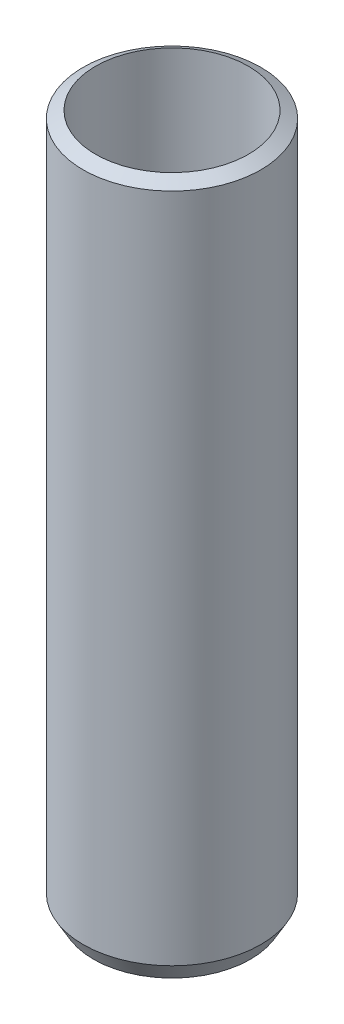
SolidWorks part; units mm, degrees
ref_plane "Front Plane" through (0, 0, 0) normal (0, 0, 1) x (1, 0, 0)
ref_plane "Top Plane" through (0, 0, 0) normal (0, 1, 0) x (1, 0, 0)
ref_plane "Right Plane" through (0, 0, 0) normal (1, 0, 0) x (0, 0, -1)
sketch "Sketch1" plane through (0, 0, 0) normal (0, 1, 0) x (1, 0, 0)
  circle A0 centre (0, 0) radius 50
  dimension "SHAFT_OD" = 100
extrude "Boss-Extrude1" add sketch "Sketch1" along normal blind 393.4649
sketch "Sketch2" plane through (0, 0, 0) normal (0, 1, 0) x (1, 0, 0)
  circle A0 centre (0, 0) radius 42.9935
  dimension "BORE_D" = 85.987
extrude "Cut-Extrude1" cut sketch "Sketch2" along normal through all
chamfer "Chamfer1" distance 5.8462 angle 60 2 edges at (0, 393.4649, 50) (0, 0, 50) first distance on face at (0, 393.4649, 50) first distance on face at (0, 0, 42.9935)
